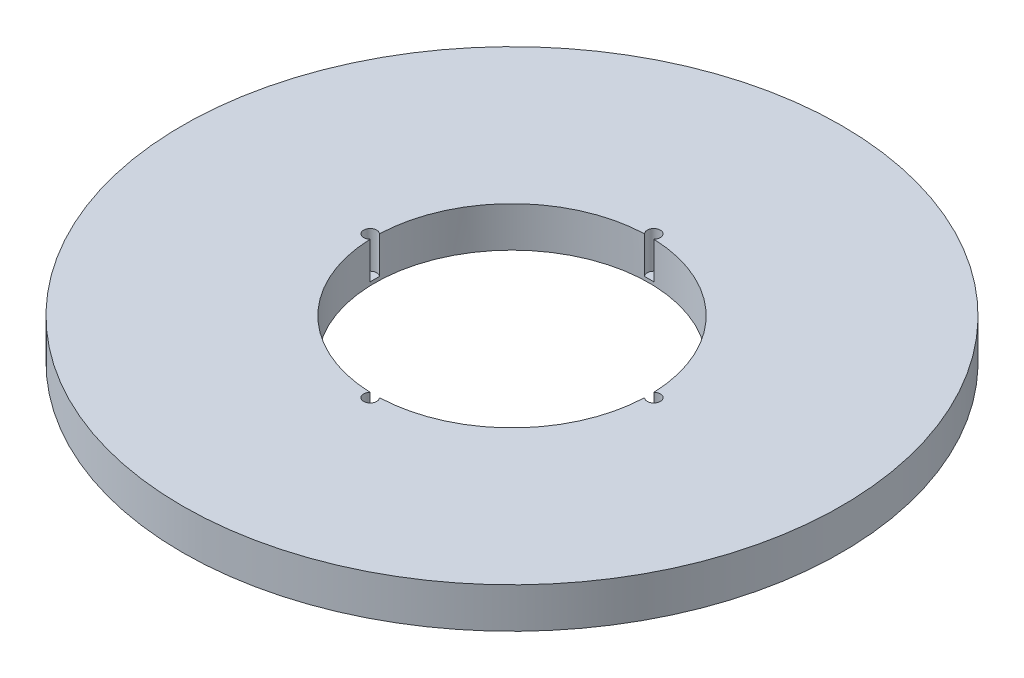
SolidWorks part; units mm, degrees
ref_plane "Front Plane" through (0, 0, 0) normal (0, 0, 1) x (1, 0, 0)
ref_plane "Top Plane" through (0, 0, 0) normal (0, 1, 0) x (1, 0, 0)
ref_plane "Right Plane" through (0, 0, 0) normal (1, 0, 0) x (0, 0, -1)
sketch "Sketch1" plane through (0, 0, 0) normal (0, 1, 0) x (1, 0, 0)
  circle A0 centre (0, 0) radius 90
  dimension "FLANGE_OD" = 180
extrude "Boss-Extrude1" add sketch "Sketch1" along normal blind 11
sketch "Sketch2" plane through (0, 0, 0) normal (0, 1, 0) x (1, 0, 0)
  circle A0 centre (0, 0) radius 37.5
  dimension "BORE_D" = 75
extrude "Cut-Extrude1" cut sketch "Sketch2" along normal through all
sketch "Sketch3" plane through (0, 11, 0) normal (0, 1, 0) x (1, 0, 0)
  circle A0 centre (0, 0) radius 38.7255 construction
  circle A1 centre (-38.7255, 0) radius 1.7908
  dimension "BOLT_D" = 3.5817
  dimension "BOLT_PCD" = 77.451
extrude "Cut-Extrude2" cut sketch "Sketch3" against normal blind 10.0957
pattern_circular "CirPattern1" count 4 over 360 about axis through (0, 0, 0) along (0, 1, 0) of "Cut-Extrude2"
